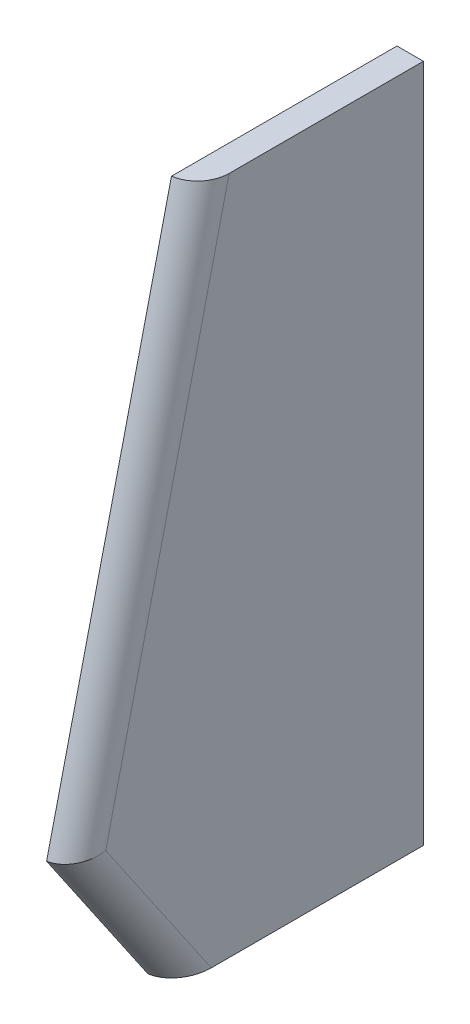
SolidWorks part; units mm, degrees
ref_plane "Front Plane" through (0, 0, 0) normal (0, 0, 1) x (1, 0, 0)
ref_plane "Top Plane" through (0, 0, 0) normal (0, 1, 0) x (1, 0, 0)
ref_plane "Right Plane" through (0, 0, 0) normal (1, 0, 0) x (0, 0, -1)
sketch "Sketch1" plane through (0, 0, 0) normal (1, 0, 0) x (0, 0, -1)
  line L0 (-20.4184, -27.6487) -> (20.2216, 145.0713)
  line L1 (20.2216, 145.0713) -> (93.5922, 145.0713)
  line L2 (93.5922, 145.0713) -> (93.5922, -75.9087) construction
  line L3 (93.5922, -75.9087) -> (12.5874, -75.9087)
  line L4 (12.5874, -75.9087) -> (-20.4184, -27.6487)
  line L5 (-20.4184, -27.6487) -> (93.5816, -27.6487)
  line L6 (93.5816, -27.6487) -> (93.5922, 145.0713)
  line L7 (93.5816, -27.6487) -> (93.5922, -75.9087)
  dimension "D1" = 114.0106
  dimension "D2" = 73.3706
  dimension "D3" = 81.0048
  dimension "D4" = 48.26
  dimension "D5" = 172.72
extrude "Boss-Extrude1" add sketch "Sketch1" along normal blind 8.6 contours L5 L6 L1 L0 | L7 L5 L4 L3 region at (0, -50.4178, -44.3702) region at (0, 52.4692, -46.0097)
fillet "Fillet1" radius 10 2 edges at (8.6, -51.7787, 3.9155) (8.6, 58.7113, 0.0984)
sketch "Sketch2" plane through (0, 0, 0) normal (-1, 0, 0) x (0, 0, 1)
  line L0 (-93.5922, -75.9087) -> (-12.5874, -75.9087)
  line L1 (-12.5874, -75.9087) -> (20.4184, -27.6487)
  line L2 (20.4184, -27.6487) -> (-20.2216, 145.0713)
  line L3 (-20.2216, 145.0713) -> (-93.5922, 145.0713)
  line L4 (-93.5922, 145.0713) -> (-93.5922, -75.9087)
  line L5 (-20.2216, 145.0713) -> (45.4511, 177.7874)
  line L6 (71.4805, -56.128) -> (20.4184, -27.6487)
  line L7 (143.9865, -20.0079) -> (71.4805, -56.128)
  line L8 (45.4511, 177.7874) -> (143.9865, -20.0079)
  dimension "D1" = 220.98
  dimension "D2" = 139.0434
  dimension "D3" = 73.3706
  dimension "D4" = 237.5787
  dimension "D5" = 165.0727
  dimension "D6" = 114.0106
  dimension "D7" = 81.0048
  dimension "D8" = 48.26
  dimension "D9" = 19.7807
  dimension "D10" = 55.9009
  dimension "D11" = 253.6961
